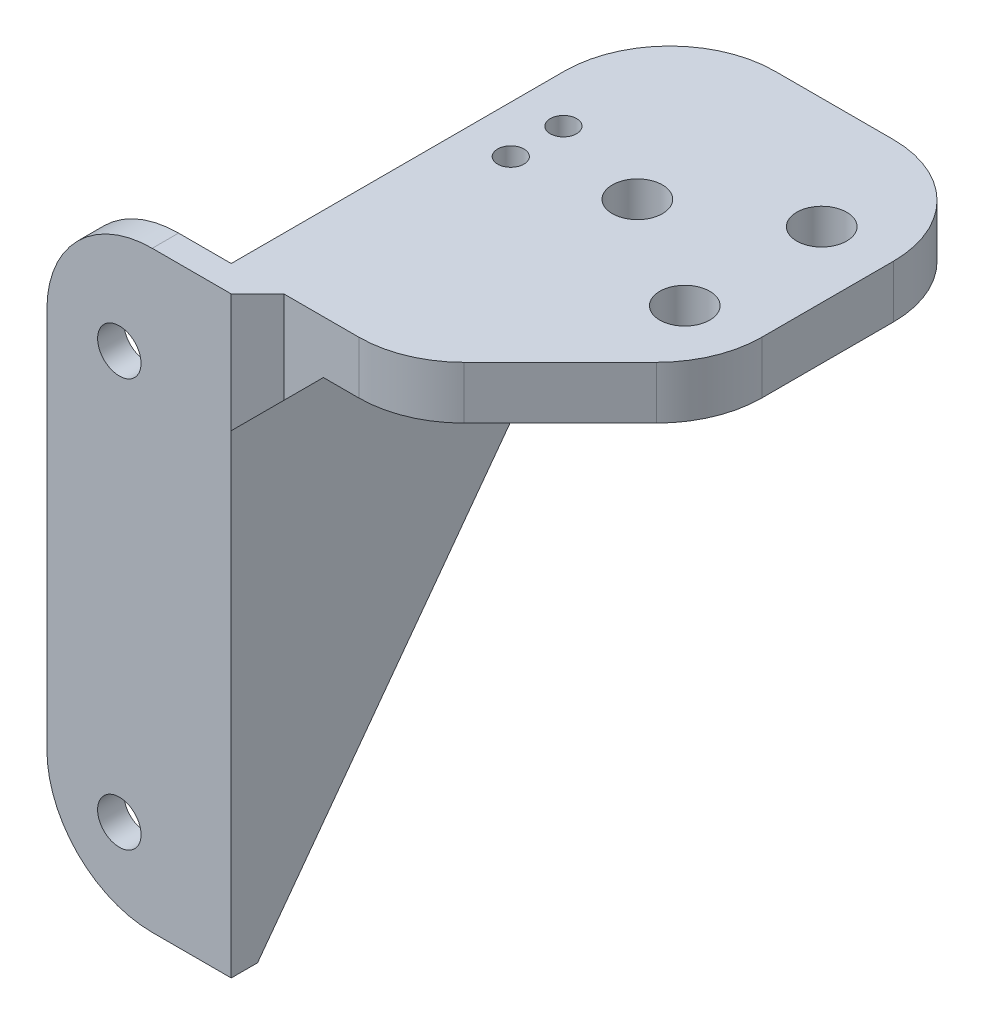
SolidWorks part; units mm, degrees
ref_plane "Front Plane" through (0, 0, 0) normal (0, 0, 1) x (1, 0, 0)
ref_plane "Top Plane" through (0, 0, 0) normal (0, 1, 0) x (1, 0, 0)
ref_plane "Right Plane" through (0, 0, 0) normal (1, 0, 0) x (0, 0, -1)
sketch "Sketch1" plane through (0, 0, 0) normal (0, 0, 1) x (1, 0, 0)
  line L0 (-6.5, 37) -> (-6.5, 6) construction
  line L1 (0, 0) -> (-12, 0)
  line L2 (0, 0) -> (0, 45)
  line L3 (0, 45) -> (-12, 45)
  line L4 (-12, 0) -> (-12, 45)
  circle A0 centre (-6.5, 37) radius 1.65
  circle A1 centre (-6.5, 6) radius 1.65
  dimension "D6" = 3.3
  dimension "D1" = 31
  dimension "D2" = 12
  dimension "D3" = 6.5
  dimension "D4" = 6
  dimension "D5" = 45
extrude "Boss-Extrude1" add sketch "Sketch1" against normal blind 2
sketch "Sketch2" plane through (0, 0, 0) normal (1, 0, 0) x (0, 0, -1)
  line L0 (35.3, 45) -> (2, 0)
  line L1 (0, 45) -> (35.3, 45)
  line L2 (0, 45) -> (0, 0)
  line L3 (0, 0) -> (2, 0)
  line L5 (2, 0) -> (2, 45) construction
  line L6 (2, 0) -> (0, 0) construction
  dimension "D1" = 35.3
extrude "Boss-Extrude2" add sketch "Sketch2" along normal blind 2
sketch "Sketch3" plane through (0, 45, 0) normal (0, 1, 0) x (1, 0, 0)
  line L0 (0, 2) -> (-12, 2) construction
  line L1 (0, 35.3) -> (25, 35.3)
  line L2 (0, 35.3) -> (0, 2)
  line L3 (0, 2) -> (25, 2)
  line L4 (25, 35.3) -> (25, 2)
  dimension "D1" = 25
  dimension "D2" = 33.3
extrude "Boss-Extrude3" add sketch "Sketch3" against normal blind 4
sketch "Sketch4" plane through (0, 45, 0) normal (0, 1, 0) x (1, 0, 0)
  line L1 (6.2, 32.85) -> (24, 32.85) construction
  line L2 (6.2, 32.85) -> (6.2, 10.45) construction
  line L3 (6.2, 10.45) -> (24, 10.45) construction
  line L4 (24, 32.85) -> (24, 10.45) construction
  line L5 (6.2, 21.65) -> (24, 21.65) construction
  line L6 (12.5, 35.3) -> (12.5, 2) construction
  line L7 (25, 35.3) -> (0, 35.3) construction
  line L8 (2, 2) -> (25, 2) construction
  line L11 (25, 2) -> (25, 35.3) construction
  circle A0 centre (20, 26.85) radius 1.9
  circle A1 centre (20, 16.45) radius 1.9
  circle A2 centre (11.2, 21.65) radius 1.9
  dimension "D3" = 3.8
  dimension "D1" = 17.8
  dimension "D2" = 22.4
  dimension "D4" = 5
  dimension "D5" = 6
  dimension "D6" = 6
  dimension "D7" = 4
  dimension "D8" = 4
  dimension "D9" = 1
  dimension "D10" = 8.45
extrude "Cut-Extrude1" cut sketch "Sketch4" against normal up to surface (4 mm away) up to face at (9, 41, -23.2133)
sketch "Sketch5" plane through (0, 45, 0) normal (0, 1, 0) x (1, 0, 0)
  line L0 (0, 21.65) -> (25, 21.65) construction
  line L1 (0, 35.3) -> (0, 2) construction
  line L3 (3.5826, 23.65) -> (3.5826, 19.65) construction
  circle A0 centre (3.5826, 23.65) radius 1
  circle A1 centre (3.5826, 19.65) radius 1
  circle A2 centre (11.2, 21.65) radius 1.9 construction
  circle A3 centre (11.2, 21.65) radius 1.9
  dimension "D1" = 2
  dimension "D2" = 4
extrude "Cut-Extrude2" cut sketch "Sketch5" against normal through all
sketch "Sketch6" plane through (0, 45, 0) normal (0, 1, 0) x (1, 0, 0)
  line L0 (13, 2) -> (25, 14)
  line L1 (2, 2) -> (25, 2) construction
  line L2 (25, 2) -> (25, 35.3) construction
  line L3 (25, 14) -> (25, 2)
  line L4 (25, 2) -> (13, 2)
  dimension "D1" = 45
  dimension "D2" = 12
extrude "Cut-Extrude3" cut sketch "Sketch6" against normal up to surface (4 mm away) up to face at (3.5826, 41, -18.65)
chamfer "Chamfer1" distance 5 angle 45 1 edges at (2, 41, -17.17)
chamfer "Chamfer2" distance 2 angle 45 1 edges at (2, 40.5, -2)
fillet "Fillet1" radius 8 2 edges at (-12, 0, -1) (-12, 45, -1)
fillet "Fillet2" radius 8 2 edges at (0, 43, -35.3) (25, 43, -35.3)
fillet "Fillet3" radius 8 2 edges at (13, 43, -2) (25, 43, -14)
